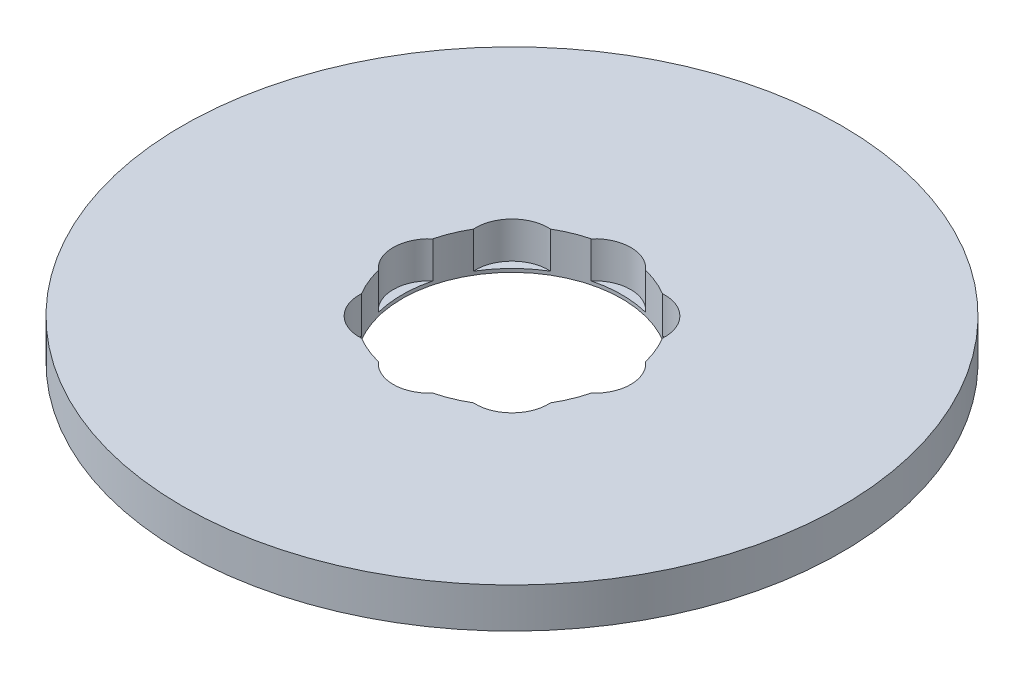
SolidWorks part; units mm, degrees
ref_plane "Front Plane" through (0, 0, 0) normal (0, 0, 1) x (1, 0, 0)
ref_plane "Top Plane" through (0, 0, 0) normal (0, 1, 0) x (1, 0, 0)
ref_plane "Right Plane" through (0, 0, 0) normal (1, 0, 0) x (0, 0, -1)
sketch "Sketch1" plane through (0, 0, 0) normal (0, 1, 0) x (1, 0, 0)
  circle A0 centre (0, 0) radius 82.5
  dimension "FLANGE_OD" = 165
extrude "Boss-Extrude1" add sketch "Sketch1" along normal blind 10
sketch "Sketch2" plane through (0, 0, 0) normal (0, 1, 0) x (1, 0, 0)
  circle A0 centre (0, 0) radius 27.5
  dimension "BORE_D" = 55
extrude "Cut-Extrude1" cut sketch "Sketch2" along normal through all
sketch "Sketch3" plane through (0, 10, 0) normal (0, 1, 0) x (1, 0, 0)
  circle A0 centre (0, 0) radius 20.6268 construction
  circle A1 centre (-20.6268, 0) radius 9.0957
  dimension "BOLT_D" = 18.1914
  dimension "BOLT_PCD" = 41.2537
extrude "Cut-Extrude2" cut sketch "Sketch3" against normal blind 9.1364
pattern_circular "CirPattern1" count 8 over 360 about axis through (0, 0, 0) along (0, 1, 0) of "Cut-Extrude2"
